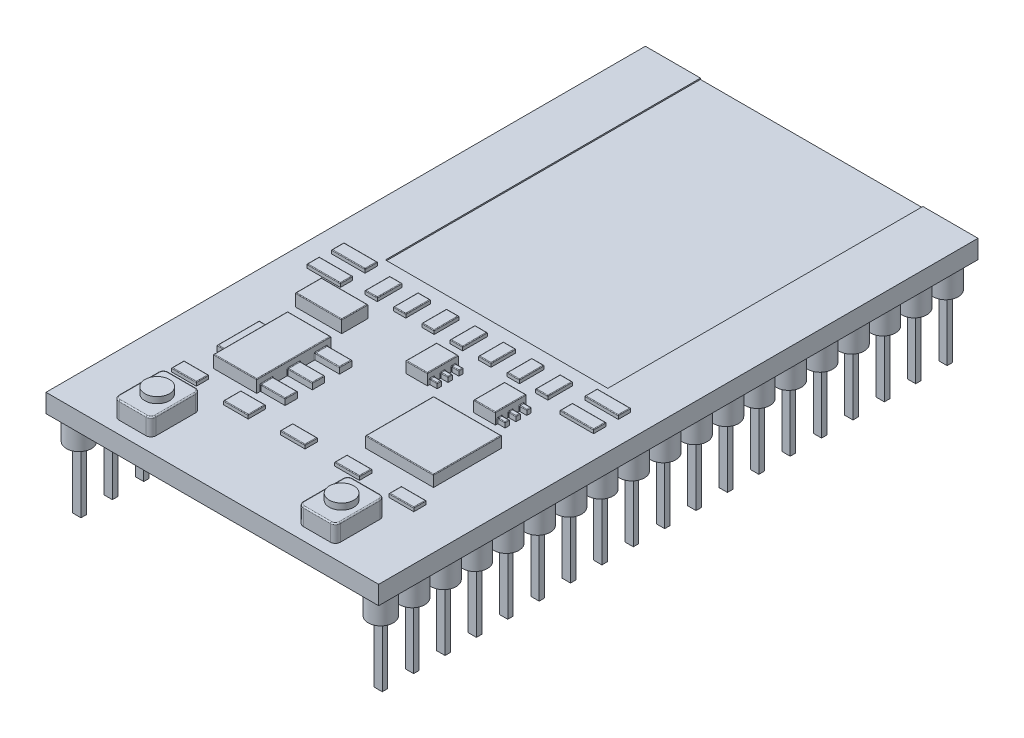
SolidWorks part; units mm, degrees
other "Markup1"
sketch "Sketch18" plane through (14.25, -8, 25.25) normal (0.0351, -0.9994, 0.0068) x (-0.8094, -0.0324, -0.5863)
sketch "Sketch19" plane through (14.25, -8, 25.25) normal (0.0351, -0.9994, 0.0068) x (-0.8094, -0.0324, -0.5863)
ref_plane "Alzado" through (0, 0, 0) normal (0, 0, 1) x (1, 0, 0)
ref_plane "Planta" through (0, 0, 0) normal (0, 1, 0) x (1, 0, 0)
ref_plane "Vista lateral" through (0, 0, 0) normal (1, 0, 0) x (0, 0, -1)
sketch "Sketch1" plane through (0, 0, 0) normal (0, 1, 0) x (1, 0, 0)
  line L0 (0, 0) -> (0, 24.257) construction
  line L1 (13.462, -24.257) -> (-13.462, -24.257)
  line L2 (13.462, -24.257) -> (13.462, 24.257)
  line L3 (13.462, 24.257) -> (-13.462, 24.257)
  line L4 (-13.462, -24.257) -> (-13.462, 24.257)
  line L5 (13.462, -24.257) -> (-13.462, 24.257) construction
  line L6 (13.462, 24.257) -> (-13.462, -24.257) construction
  line L7 (13.462, 0) -> (-13.462, 0) construction
  line L12 (11.462, 24.257) -> (11.462, 22.257) construction
  point P0 (0, 0)
  point P6 (13.462, 23.257)
  point P7 (12.462, 24.257)
  point P8 (17.05, 25.3)
  point P29 (11.462, 24.257)
  point P30 (-13.462, 24.257)
  point P31 (13.462, 24.257)
  point P32 (13.462, -24.257)
  point P33 (-13.462, -24.257)
  dimension "D1" = 48.514
  dimension "D2" = 26.924
  dimension "D3" = 1
  dimension "D4" = 1
  dimension "D6" = 2
  dimension "D7" = 2
extrude "Boss-Extrude1" add sketch "Sketch1" along normal blind 1.5 contours L1 L2 L3 L4 region at (0, 0, 0)
sketch "Sketch2" plane through (0, 0, 0) normal (0, -1, 0) x (1, 0, 0)
  line L0 (0, -24.257) -> (0, 24.257) construction
  line L1 (13.462, -24.257) -> (-13.462, -24.257) construction
  line L2 (13.462, 24.257) -> (-13.462, 24.257) construction
  line L3 (13.462, 0) -> (-13.462, 0) construction
  line L4 (13.462, 24.257) -> (13.462, -24.257) construction
  line L5 (-13.462, 24.257) -> (-13.462, -24.257) construction
  line L6 (-12.962, -23.0261) -> (-12.962, 24.257) construction
  line L7 (-12.962, -23.0261) -> (-12.962, -24.257) construction
  line L8 (-12.812, -19.067) -> (-12.712, -18.967)
  line L9 (-13.112, -18.567) -> (-12.812, -18.567)
  line L10 (-13.212, -18.667) -> (-13.212, -18.967)
  line L11 (-13.112, -19.067) -> (-12.812, -19.067)
  line L12 (-12.712, -18.667) -> (-12.712, -18.967)
  line L13 (-13.212, -18.567) -> (-12.712, -19.067) construction
  line L14 (-13.212, -19.067) -> (-12.712, -18.567) construction
  line L15 (-13.212, -18.967) -> (-13.112, -19.067)
  line L16 (-13.212, -18.667) -> (-13.112, -18.567)
  line L17 (-12.812, -18.567) -> (-12.712, -18.667)
  line L18 (-13.212, -16.427) -> (-13.112, -16.527)
  line L19 (-13.112, -16.527) -> (-12.812, -16.527)
  line L20 (-12.812, -16.527) -> (-12.712, -16.427)
  line L21 (-12.712, -16.127) -> (-12.712, -16.427)
  line L22 (-12.812, -16.027) -> (-12.712, -16.127)
  line L23 (-13.112, -16.027) -> (-12.812, -16.027)
  line L24 (-13.212, -16.127) -> (-13.112, -16.027)
  line L25 (-13.212, -16.127) -> (-13.212, -16.427)
  line L26 (-13.212, -13.887) -> (-13.112, -13.987)
  line L27 (-13.112, -13.987) -> (-12.812, -13.987)
  line L28 (-12.812, -13.987) -> (-12.712, -13.887)
  line L29 (-12.712, -13.587) -> (-12.712, -13.887)
  line L30 (-12.812, -13.487) -> (-12.712, -13.587)
  line L31 (-13.112, -13.487) -> (-12.812, -13.487)
  line L32 (-13.212, -13.587) -> (-13.112, -13.487)
  line L33 (-13.212, -13.587) -> (-13.212, -13.887)
  line L34 (-13.212, -11.347) -> (-13.112, -11.447)
  line L35 (-13.112, -11.447) -> (-12.812, -11.447)
  line L36 (-12.812, -11.447) -> (-12.712, -11.347)
  line L37 (-12.712, -11.047) -> (-12.712, -11.347)
  line L38 (-12.812, -10.947) -> (-12.712, -11.047)
  line L39 (-13.112, -10.947) -> (-12.812, -10.947)
  line L40 (-13.212, -11.047) -> (-13.112, -10.947)
  line L41 (-13.212, -11.047) -> (-13.212, -11.347)
  line L42 (-13.212, -8.807) -> (-13.112, -8.907)
  line L43 (-13.112, -8.907) -> (-12.812, -8.907)
  line L44 (-12.812, -8.907) -> (-12.712, -8.807)
  line L45 (-12.712, -8.507) -> (-12.712, -8.807)
  line L46 (-12.812, -8.407) -> (-12.712, -8.507)
  line L47 (-13.112, -8.407) -> (-12.812, -8.407)
  line L48 (-13.212, -8.507) -> (-13.112, -8.407)
  line L49 (-13.212, -8.507) -> (-13.212, -8.807)
  line L50 (-13.212, -6.267) -> (-13.112, -6.367)
  line L51 (-13.112, -6.367) -> (-12.812, -6.367)
  line L52 (-12.812, -6.367) -> (-12.712, -6.267)
  line L53 (-12.712, -5.967) -> (-12.712, -6.267)
  line L54 (-12.812, -5.867) -> (-12.712, -5.967)
  line L55 (-13.112, -5.867) -> (-12.812, -5.867)
  line L56 (-13.212, -5.967) -> (-13.112, -5.867)
  line L57 (-13.212, -5.967) -> (-13.212, -6.267)
  line L58 (-13.212, -3.727) -> (-13.112, -3.827)
  line L59 (-13.112, -3.827) -> (-12.812, -3.827)
  line L60 (-12.812, -3.827) -> (-12.712, -3.727)
  line L61 (-12.712, -3.427) -> (-12.712, -3.727)
  line L62 (-12.812, -3.327) -> (-12.712, -3.427)
  line L63 (-13.112, -3.327) -> (-12.812, -3.327)
  line L64 (-13.212, -3.427) -> (-13.112, -3.327)
  line L65 (-13.212, -3.427) -> (-13.212, -3.727)
  line L66 (-13.212, -1.187) -> (-13.112, -1.287)
  line L67 (-13.112, -1.287) -> (-12.812, -1.287)
  line L68 (-12.812, -1.287) -> (-12.712, -1.187)
  line L69 (-12.712, -0.887) -> (-12.712, -1.187)
  line L70 (-12.812, -0.787) -> (-12.712, -0.887)
  line L71 (-13.112, -0.787) -> (-12.812, -0.787)
  line L72 (-13.212, -0.887) -> (-13.112, -0.787)
  line L73 (-13.212, -0.887) -> (-13.212, -1.187)
  line L74 (-13.212, 1.353) -> (-13.112, 1.253)
  line L75 (-13.112, 1.253) -> (-12.812, 1.253)
  line L76 (-12.812, 1.253) -> (-12.712, 1.353)
  line L77 (-12.712, 1.653) -> (-12.712, 1.353)
  line L78 (-12.812, 1.753) -> (-12.712, 1.653)
  line L79 (-13.112, 1.753) -> (-12.812, 1.753)
  line L80 (-13.212, 1.653) -> (-13.112, 1.753)
  line L81 (-13.212, 1.653) -> (-13.212, 1.353)
  line L82 (-13.212, 3.893) -> (-13.112, 3.793)
  line L83 (-13.112, 3.793) -> (-12.812, 3.793)
  line L84 (-12.812, 3.793) -> (-12.712, 3.893)
  line L85 (-12.712, 4.193) -> (-12.712, 3.893)
  line L86 (-12.812, 4.293) -> (-12.712, 4.193)
  line L87 (-13.112, 4.293) -> (-12.812, 4.293)
  line L88 (-13.212, 4.193) -> (-13.112, 4.293)
  line L89 (-13.212, 4.193) -> (-13.212, 3.893)
  line L90 (-13.212, 6.433) -> (-13.112, 6.333)
  line L91 (-13.112, 6.333) -> (-12.812, 6.333)
  line L92 (-12.812, 6.333) -> (-12.712, 6.433)
  line L93 (-12.712, 6.733) -> (-12.712, 6.433)
  line L94 (-12.812, 6.833) -> (-12.712, 6.733)
  line L95 (-13.112, 6.833) -> (-12.812, 6.833)
  line L96 (-13.212, 6.733) -> (-13.112, 6.833)
  line L97 (-13.212, 6.733) -> (-13.212, 6.433)
  line L98 (-13.212, 8.973) -> (-13.112, 8.873)
  line L99 (-13.112, 8.873) -> (-12.812, 8.873)
  line L100 (-12.812, 8.873) -> (-12.712, 8.973)
  line L101 (-12.712, 9.273) -> (-12.712, 8.973)
  line L102 (-12.812, 9.373) -> (-12.712, 9.273)
  line L103 (-13.112, 9.373) -> (-12.812, 9.373)
  line L104 (-13.212, 9.273) -> (-13.112, 9.373)
  line L105 (-13.212, 9.273) -> (-13.212, 8.973)
  line L106 (-13.212, 11.513) -> (-13.112, 11.413)
  line L107 (-13.112, 11.413) -> (-12.812, 11.413)
  line L108 (-12.812, 11.413) -> (-12.712, 11.513)
  line L109 (-12.712, 11.813) -> (-12.712, 11.513)
  line L110 (-12.812, 11.913) -> (-12.712, 11.813)
  line L111 (-13.112, 11.913) -> (-12.812, 11.913)
  line L112 (-13.212, 11.813) -> (-13.112, 11.913)
  line L113 (-13.212, 11.813) -> (-13.212, 11.513)
  line L114 (-13.212, 14.053) -> (-13.112, 13.953)
  line L115 (-13.112, 13.953) -> (-12.812, 13.953)
  line L116 (-12.812, 13.953) -> (-12.712, 14.053)
  line L117 (-12.712, 14.353) -> (-12.712, 14.053)
  line L118 (-12.812, 14.453) -> (-12.712, 14.353)
  line L119 (-13.112, 14.453) -> (-12.812, 14.453)
  line L120 (-13.212, 14.353) -> (-13.112, 14.453)
  line L121 (-13.212, 14.353) -> (-13.212, 14.053)
  line L122 (-13.212, 16.593) -> (-13.112, 16.493)
  line L123 (-13.112, 16.493) -> (-12.812, 16.493)
  line L124 (-12.812, 16.493) -> (-12.712, 16.593)
  line L125 (-12.712, 16.893) -> (-12.712, 16.593)
  line L126 (-12.812, 16.993) -> (-12.712, 16.893)
  line L127 (-13.112, 16.993) -> (-12.812, 16.993)
  line L128 (-13.212, 16.893) -> (-13.112, 16.993)
  line L129 (-13.212, 16.893) -> (-13.212, 16.593)
  line L130 (12.812, 16.493) -> (12.712, 16.593)
  line L131 (12.712, 16.893) -> (12.712, 16.593)
  line L132 (12.812, 16.993) -> (12.712, 16.893)
  line L133 (13.112, 16.993) -> (12.812, 16.993)
  line L134 (13.212, 16.893) -> (13.112, 16.993)
  line L135 (13.212, 16.893) -> (13.212, 16.593)
  line L136 (13.212, 16.593) -> (13.112, 16.493)
  line L137 (13.112, 16.493) -> (12.812, 16.493)
  line L138 (13.212, 14.353) -> (13.212, 14.053)
  line L139 (13.212, 14.053) -> (13.112, 13.953)
  line L140 (13.112, 13.953) -> (12.812, 13.953)
  line L141 (12.812, 13.953) -> (12.712, 14.053)
  line L142 (12.712, 14.353) -> (12.712, 14.053)
  line L143 (12.812, 14.453) -> (12.712, 14.353)
  line L144 (13.112, 14.453) -> (12.812, 14.453)
  line L145 (13.212, 14.353) -> (13.112, 14.453)
  line L146 (13.212, 11.813) -> (13.212, 11.513)
  line L147 (13.212, 11.513) -> (13.112, 11.413)
  line L148 (13.112, 11.413) -> (12.812, 11.413)
  line L149 (12.812, 11.413) -> (12.712, 11.513)
  line L150 (12.712, 11.813) -> (12.712, 11.513)
  line L151 (12.812, 11.913) -> (12.712, 11.813)
  line L152 (13.112, 11.913) -> (12.812, 11.913)
  line L153 (13.212, 11.813) -> (13.112, 11.913)
  line L154 (13.212, 9.273) -> (13.212, 8.973)
  line L155 (13.212, 8.973) -> (13.112, 8.873)
  line L156 (13.112, 8.873) -> (12.812, 8.873)
  line L157 (12.812, 8.873) -> (12.712, 8.973)
  line L158 (12.712, 9.273) -> (12.712, 8.973)
  line L159 (12.812, 9.373) -> (12.712, 9.273)
  line L160 (13.112, 9.373) -> (12.812, 9.373)
  line L161 (13.212, 9.273) -> (13.112, 9.373)
  line L162 (13.212, 6.733) -> (13.212, 6.433)
  line L163 (13.212, 6.433) -> (13.112, 6.333)
  line L164 (13.112, 6.333) -> (12.812, 6.333)
  line L165 (12.812, 6.333) -> (12.712, 6.433)
  line L166 (12.712, 6.733) -> (12.712, 6.433)
  line L167 (12.812, 6.833) -> (12.712, 6.733)
  line L168 (13.112, 6.833) -> (12.812, 6.833)
  line L169 (13.212, 6.733) -> (13.112, 6.833)
  line L170 (13.212, 4.193) -> (13.212, 3.893)
  line L171 (13.212, 3.893) -> (13.112, 3.793)
  line L172 (13.112, 3.793) -> (12.812, 3.793)
  line L173 (12.812, 3.793) -> (12.712, 3.893)
  line L174 (12.712, 4.193) -> (12.712, 3.893)
  line L175 (12.812, 4.293) -> (12.712, 4.193)
  line L176 (13.112, 4.293) -> (12.812, 4.293)
  line L177 (13.212, 4.193) -> (13.112, 4.293)
  line L178 (13.212, 1.653) -> (13.212, 1.353)
  line L179 (13.212, 1.353) -> (13.112, 1.253)
  line L180 (13.112, 1.253) -> (12.812, 1.253)
  line L181 (12.812, 1.253) -> (12.712, 1.353)
  line L182 (12.712, 1.653) -> (12.712, 1.353)
  line L183 (12.812, 1.753) -> (12.712, 1.653)
  line L184 (13.112, 1.753) -> (12.812, 1.753)
  line L185 (13.212, 1.653) -> (13.112, 1.753)
  line L186 (13.212, -0.887) -> (13.212, -1.187)
  line L187 (13.212, -1.187) -> (13.112, -1.287)
  line L188 (13.112, -1.287) -> (12.812, -1.287)
  line L189 (12.812, -1.287) -> (12.712, -1.187)
  line L190 (12.712, -0.887) -> (12.712, -1.187)
  line L191 (12.812, -0.787) -> (12.712, -0.887)
  line L192 (13.112, -0.787) -> (12.812, -0.787)
  line L193 (13.212, -0.887) -> (13.112, -0.787)
  line L194 (13.212, -3.427) -> (13.212, -3.727)
  line L195 (13.212, -3.727) -> (13.112, -3.827)
  line L196 (13.112, -3.827) -> (12.812, -3.827)
  line L197 (12.812, -3.827) -> (12.712, -3.727)
  line L198 (12.712, -3.427) -> (12.712, -3.727)
  line L199 (12.812, -3.327) -> (12.712, -3.427)
  line L200 (13.112, -3.327) -> (12.812, -3.327)
  line L201 (13.212, -3.427) -> (13.112, -3.327)
  line L202 (13.212, -5.967) -> (13.212, -6.267)
  line L203 (13.212, -6.267) -> (13.112, -6.367)
  line L204 (13.112, -6.367) -> (12.812, -6.367)
  line L205 (12.812, -6.367) -> (12.712, -6.267)
  line L206 (12.712, -5.967) -> (12.712, -6.267)
  line L207 (12.812, -5.867) -> (12.712, -5.967)
  line L208 (13.112, -5.867) -> (12.812, -5.867)
  line L209 (13.212, -5.967) -> (13.112, -5.867)
  line L210 (13.212, -8.507) -> (13.212, -8.807)
  line L211 (13.212, -8.807) -> (13.112, -8.907)
  line L212 (13.112, -8.907) -> (12.812, -8.907)
  line L213 (12.812, -8.907) -> (12.712, -8.807)
  line L214 (12.712, -8.507) -> (12.712, -8.807)
  line L215 (12.812, -8.407) -> (12.712, -8.507)
  line L216 (13.112, -8.407) -> (12.812, -8.407)
  line L217 (13.212, -8.507) -> (13.112, -8.407)
  line L218 (13.212, -11.047) -> (13.212, -11.347)
  line L219 (13.212, -11.347) -> (13.112, -11.447)
  line L220 (13.112, -11.447) -> (12.812, -11.447)
  line L221 (12.812, -11.447) -> (12.712, -11.347)
  line L222 (12.712, -11.047) -> (12.712, -11.347)
  line L223 (12.812, -10.947) -> (12.712, -11.047)
  line L224 (13.112, -10.947) -> (12.812, -10.947)
  line L225 (13.212, -11.047) -> (13.112, -10.947)
  line L226 (13.212, -13.587) -> (13.212, -13.887)
  line L227 (13.212, -13.887) -> (13.112, -13.987)
  line L228 (13.112, -13.987) -> (12.812, -13.987)
  line L229 (12.812, -13.987) -> (12.712, -13.887)
  line L230 (12.712, -13.587) -> (12.712, -13.887)
  line L231 (12.812, -13.487) -> (12.712, -13.587)
  line L232 (13.112, -13.487) -> (12.812, -13.487)
  line L233 (13.212, -13.587) -> (13.112, -13.487)
  line L234 (13.212, -16.127) -> (13.212, -16.427)
  line L235 (13.212, -16.427) -> (13.112, -16.527)
  line L236 (13.112, -16.527) -> (12.812, -16.527)
  line L237 (12.812, -16.527) -> (12.712, -16.427)
  line L238 (12.712, -16.127) -> (12.712, -16.427)
  line L239 (12.812, -16.027) -> (12.712, -16.127)
  line L240 (13.112, -16.027) -> (12.812, -16.027)
  line L241 (13.212, -16.127) -> (13.112, -16.027)
  line L242 (13.212, -18.667) -> (13.212, -18.967)
  line L243 (13.212, -18.967) -> (13.112, -19.067)
  line L244 (13.112, -19.067) -> (12.812, -19.067)
  line L245 (12.812, -19.067) -> (12.712, -18.967)
  line L246 (12.712, -18.667) -> (12.712, -18.967)
  line L247 (12.812, -18.567) -> (12.712, -18.667)
  line L248 (13.112, -18.567) -> (12.812, -18.567)
  line L249 (13.212, -18.667) -> (13.112, -18.567)
  point P12 (-14.25, -25.25)
  point P13 (-13.462, -21.6118)
  point P14 (-12.962, -23.0261)
  point P18 (-12.962, -18.817)
  point P19 (-12.962, -18.817)
  dimension "D1" = 1.5
  dimension "D2" = 5.44
  dimension "D3" = 0.5
  dimension "D4" = 0.5
  dimension "D5" = 15
  dimension "D6" = 15
sketch "Sketch5" plane through (0, 1.5, 0) normal (0, 1, 0) x (1, 0, 0)
  line L0 (-13.462, -23.257) -> (-8.962, -23.257) construction
  line L1 (0, -24.257) -> (0, 24.257) construction
  line L2 (-8.562, -23.257) -> (-6.362, -23.257)
  line L3 (-8.962, -22.857) -> (-8.962, -19.657)
  line L4 (-8.562, -19.257) -> (-6.362, -19.257)
  line L5 (-5.962, -22.857) -> (-5.962, -19.657)
  line L6 (13.462, -24.257) -> (-13.462, -24.257) construction
  line L7 (13.462, 24.257) -> (-13.462, 24.257) construction
  line L8 (5.962, -22.857) -> (5.962, -19.657)
  line L9 (8.562, -23.257) -> (6.362, -23.257)
  line L10 (8.962, -22.857) -> (8.962, -19.657)
  line L11 (8.562, -19.257) -> (6.362, -19.257)
  arc A0 (-8.962, -22.857) -> (-8.562, -23.257) centre (-8.562, -22.857) ccw
  arc A1 (-6.362, -23.257) -> (-5.962, -22.857) centre (-6.362, -22.857) ccw
  arc A2 (-6.362, -19.257) -> (-5.962, -19.657) centre (-6.362, -19.657) cw
  arc A3 (-8.962, -19.657) -> (-8.562, -19.257) centre (-8.562, -19.657) cw
  arc A4 (6.362, -23.257) -> (5.962, -22.857) centre (6.362, -22.857) cw
  arc A5 (8.962, -22.857) -> (8.562, -23.257) centre (8.562, -22.857) cw
  arc A6 (8.962, -19.657) -> (8.562, -19.257) centre (8.562, -19.657) ccw
  arc A7 (6.362, -19.257) -> (5.962, -19.657) centre (6.362, -19.657) ccw
  point P11 (-5.962, -23.257)
  point P14 (-5.962, -19.257)
  point P17 (-8.962, -19.257)
  dimension "D4" = 0.4
  dimension "D1" = 4.5
  dimension "D2" = 4
  dimension "D3" = 3
extrude "Boss-Extrude5" add sketch "Sketch5" along normal blind 1.4
sketch "Sketch6" plane through (0, 2.9, 0) normal (0, 1, 0) x (1, 0, 0)
  line L0 (-8.962, -21.257) -> (-5.962, -21.257) construction
  line L1 (-8.962, -19.657) -> (-8.962, -22.857) construction
  line L2 (-5.962, -22.857) -> (-5.962, -19.657) construction
  line L3 (0, -24.257) -> (0, 24.257) construction
  line L4 (13.462, -24.257) -> (-13.462, -24.257) construction
  line L5 (13.462, 24.257) -> (-13.462, 24.257) construction
  circle A0 centre (-7.462, -21.257) radius 0.9958
  circle A1 centre (7.462, -21.257) radius 0.9958
extrude "Boss-Extrude6" add sketch "Sketch6" along normal blind 0.5
sketch "Sketch7" plane through (0, 1.5, 0) normal (0, 1, 0) x (1, 0, 0)
  line L0 (13.462, 24.257) -> (-13.462, 24.257) construction
  line L1 (0, 24.257) -> (0, 0) construction
  line L3 (-9, 24.257) -> (9, 24.257)
  line L4 (-9, 24.257) -> (-9, -1.243)
  line L5 (-9, -1.243) -> (9, -1.243)
  line L6 (9, 24.257) -> (9, -1.243)
  point P0 (0, 24.257)
  point P5 (-9, 24.257)
  dimension "D1" = 9
  dimension "D2" = 18
  dimension "D3" = 25.5
extrude "Cut-Extrude1" cut sketch "Sketch7" against normal blind 0.1
sketch "Sketch8" plane through (0, 1.5, 0) normal (0, 1, 0) x (1, 0, 0)
  line L0 (13.462, -24.257) -> (-13.462, -24.257) construction
  line L1 (0, -24.257) -> (0, 0) construction
  line L2 (2.8, -4.5) -> (2.8, -2.5)
  line L3 (0.5, -4.5) -> (-0.5, -4.5)
  line L4 (1, -17.75) -> (-1, -17.75)
  line L5 (1, -17.75) -> (1, -16.75)
  line L6 (1, -16.75) -> (-1, -16.75)
  line L7 (-1, -17.75) -> (-1, -16.75)
  line L8 (1, -17.75) -> (-1, -16.75) construction
  line L9 (1, -16.75) -> (-1, -17.75) construction
  line L10 (-3.4, -17.95) -> (-5.4, -17.95)
  line L11 (-3.4, -17.95) -> (-3.4, -16.55)
  line L12 (-3.4, -16.55) -> (-5.4, -16.55)
  line L13 (-5.4, -17.95) -> (-5.4, -16.55)
  line L14 (-3.4, -17.95) -> (-5.4, -16.55) construction
  line L15 (-3.4, -16.55) -> (-5.4, -17.95) construction
  line L16 (-9.8, -17.75) -> (-7.8, -17.75)
  line L17 (-9.8, -17.75) -> (-9.8, -16.75)
  line L18 (-9.8, -16.75) -> (-7.8, -16.75)
  line L19 (-7.8, -17.75) -> (-7.8, -16.75)
  line L20 (-9.8, -17.75) -> (-7.8, -16.75) construction
  line L21 (-9.8, -16.75) -> (-7.8, -17.75) construction
  line L22 (5.4, -17.75) -> (3.4, -17.75)
  line L23 (5.4, -17.75) -> (5.4, -16.75)
  line L24 (5.4, -16.75) -> (3.4, -16.75)
  line L25 (3.4, -17.75) -> (3.4, -16.75)
  line L26 (5.4, -17.75) -> (3.4, -16.75) construction
  line L27 (5.4, -16.75) -> (3.4, -17.75) construction
  line L28 (9.8, -17.75) -> (7.8, -17.75)
  line L29 (9.8, -17.75) -> (9.8, -16.75)
  line L30 (9.8, -16.75) -> (7.8, -16.75)
  line L31 (7.8, -17.75) -> (7.8, -16.75)
  line L32 (9.8, -17.75) -> (7.8, -16.75) construction
  line L33 (9.8, -16.75) -> (7.8, -17.75) construction
  line L34 (0.5, -4.5) -> (0.5, -2.5)
  line L35 (0.5, -2.5) -> (-0.5, -2.5)
  line L36 (-0.5, -4.5) -> (-0.5, -2.5)
  line L37 (0.5, -4.5) -> (-0.5, -2.5) construction
  line L38 (0.5, -2.5) -> (-0.5, -4.5) construction
  line L39 (2.8, -2.5) -> (1.8, -2.5)
  line L40 (1.8, -4.5) -> (1.8, -2.5)
  line L41 (2.8, -4.5) -> (1.8, -4.5)
  line L42 (5.1, -4.5) -> (5.1, -2.5)
  line L43 (5.1, -2.5) -> (4.1, -2.5)
  line L44 (4.1, -4.5) -> (4.1, -2.5)
  line L45 (5.1, -4.5) -> (4.1, -4.5)
  line L46 (7.4, -4.5) -> (7.4, -2.5)
  line L47 (7.4, -2.5) -> (6.4, -2.5)
  line L48 (6.4, -4.5) -> (6.4, -2.5)
  line L49 (7.4, -4.5) -> (6.4, -4.5)
  line L50 (-7.4, -4.5) -> (-6.4, -4.5)
  line L51 (-6.4, -4.5) -> (-6.4, -2.5)
  line L52 (-7.4, -2.5) -> (-6.4, -2.5)
  line L53 (-7.4, -4.5) -> (-7.4, -2.5)
  line L54 (-5.1, -4.5) -> (-4.1, -4.5)
  line L55 (-4.1, -4.5) -> (-4.1, -2.5)
  line L56 (-5.1, -2.5) -> (-4.1, -2.5)
  line L57 (-5.1, -4.5) -> (-5.1, -2.5)
  line L58 (-2.8, -4.5) -> (-1.8, -4.5)
  line L59 (-1.8, -4.5) -> (-1.8, -2.5)
  line L60 (-2.8, -2.5) -> (-1.8, -2.5)
  line L61 (-2.8, -4.5) -> (-2.8, -2.5)
  line L62 (7.4, -3.5) -> (13.462, -3.5) construction
  line L63 (13.462, -24.257) -> (13.462, 24.257) construction
  line L64 (11.6049, -3) -> (11.6049, -2)
  line L65 (11.6049, -5) -> (8.8951, -5)
  line L66 (11.6049, -5) -> (11.6049, -4)
  line L67 (11.6049, -2) -> (8.8951, -2)
  line L68 (8.8951, -5) -> (8.8951, -4)
  line L69 (11.6049, -5) -> (8.8951, -2) construction
  line L70 (11.6049, -2) -> (8.8951, -5) construction
  line L71 (11.6049, -4) -> (8.8951, -4)
  line L72 (8.8951, -3) -> (8.8951, -2)
  line L73 (11.6049, -3) -> (8.8951, -3)
  line L74 (-11.6049, -5) -> (-8.8951, -5)
  line L75 (11.6049, -4) -> (8.8951, -3) construction
  line L76 (11.6049, -3) -> (8.8951, -4) construction
  line L77 (-8.8951, -5) -> (-8.8951, -4)
  line L78 (-11.6049, -4) -> (-8.8951, -4)
  line L79 (-11.6049, -5) -> (-11.6049, -4)
  line L80 (-11.6049, -3) -> (-11.6049, -2)
  line L81 (-11.6049, -3) -> (-8.8951, -3)
  line L82 (-8.8951, -3) -> (-8.8951, -2)
  line L83 (-11.6049, -2) -> (-8.8951, -2)
  point P0 (0, -24.257)
  point P6 (0, -17.25)
  point P7 (-4.4, -17.25)
  point P8 (-8.8, -17.25)
  point P9 (-4.4, -17.25)
  point P10 (0, -17.25)
  point P17 (4.4, -17.25)
  point P18 (8.8, -17.25)
  point P21 (-8.8, -17.25)
  point P26 (4.4, -17.25)
  point P31 (8.8, -17.25)
  point P36 (0, -3.5)
  point P37 (0, -3.5)
  point P70 (10.25, -3.5)
  point P71 (10.25, -3.5)
  point P76 (10.25, -3.5)
  dimension "D1" = 3
  dimension "D2" = 2
  dimension "D3" = 1
  dimension "D4" = 2
  dimension "D5" = 1.4
  dimension "D6" = 2
  dimension "D7" = 1
  dimension "D8" = 2
  dimension "D9" = 2
  dimension "D11" = 1
extrude "Boss-Extrude7" add sketch "Sketch8" along normal blind 0.3
sketch "Sketch9" plane through (0, 1.5, 0) normal (0, 1, 0) x (1, 0, 0)
  line L0 (3.4, -16.75) -> (3.4, -1.243) construction
  line L1 (-9, -1.243) -> (9, -1.243) construction
  line L2 (5.1, -4.5) -> (6.4, -4.5) construction
  line L3 (3.4, -15.25) -> (8.9, -15.25)
  line L4 (3.4, -15.25) -> (3.4, -9.75)
  line L5 (3.4, -9.75) -> (8.9, -9.75)
  line L6 (8.9, -15.25) -> (8.9, -9.75)
  line L7 (6.15, -9.75) -> (6.15, -4.5) construction
  line L8 (-0.225, -8.375) -> (-0.225, -5.875)
  line L9 (7.025, -8.375) -> (5.275, -8.375)
  line L10 (7.025, -8.375) -> (7.025, -5.875)
  line L11 (7.025, -5.875) -> (5.275, -5.875)
  line L12 (5.275, -8.375) -> (5.275, -5.875)
  line L13 (7.025, -8.375) -> (5.275, -5.875) construction
  line L14 (7.025, -5.875) -> (5.275, -8.375) construction
  line L15 (-0.225, -8.375) -> (1.525, -8.375)
  line L16 (1.525, -8.375) -> (1.525, -5.875)
  line L17 (-0.225, -5.875) -> (1.525, -5.875)
  point P5 (3.4, -15.25)
  point P16 (6.15, -7.125)
  point P17 (6.15, -7.125)
  dimension "D1" = 1.75
  dimension "D2" = 1.5
  dimension "D3" = 5.5
  dimension "D4" = 2.5
  dimension "D5" = 5.5
extrude "Boss-Extrude8" add sketch "Sketch9" along normal blind 0.9
sketch "Sketch10" plane through (0, 1.5, 0) normal (0, 1, 0) x (1, 0, 0)
  line L0 (-9.8, -17.25) -> (-3.4, -17.25) construction
  line L1 (-9.8, -16.75) -> (-9.8, -17.75) construction
  line L2 (-3.4, -17.95) -> (-3.4, -16.55) construction
  line L3 (-0.225, -8.375) -> (-13.462, -8.375) construction
  line L4 (-13.462, -24.257) -> (-13.462, 24.257) construction
  line L5 (-6.6, -17.25) -> (-6.6, -8.375) construction
  line L7 (-4.85, -15.8125) -> (-8.35, -15.8125)
  line L8 (-4.85, -15.8125) -> (-4.85, -9.8125)
  line L9 (-4.85, -9.8125) -> (-8.35, -9.8125)
  line L10 (-8.35, -15.8125) -> (-8.35, -9.8125)
  line L11 (-4.85, -15.8125) -> (-8.35, -9.8125) construction
  line L12 (-4.85, -9.8125) -> (-8.35, -15.8125) construction
  point P13 (-6.6, -12.8125)
  dimension "D1" = 6
  dimension "D2" = 3.5
extrude "Boss-Extrude9" add sketch "Sketch10" along normal blind 1
sketch "Sketch11" plane through (0, 1.5, 0) normal (0, 1, 0) x (1, 0, 0)
  line L0 (-4.85, -12.8125) -> (-8.35, -12.8125) construction
  line L1 (-4.85, -15.8125) -> (-4.85, -9.8125) construction
  line L2 (-8.35, -9.8125) -> (-8.35, -15.8125) construction
  line L3 (-4.85, -12.8125) -> (-4.85, -11.1125) construction
  line L4 (-4.85, -15.8125) -> (-4.85, -9.8125) construction
  line L5 (-4.85, -12.3125) -> (-2.85, -12.3125)
  line L6 (-4.85, -11.1125) -> (-2.85, -11.1125)
  line L7 (-4.85, -11.1125) -> (-4.85, -10.1125)
  line L8 (-4.85, -10.1125) -> (-2.85, -10.1125)
  line L9 (-2.85, -11.1125) -> (-2.85, -10.1125)
  line L10 (-2.85, -13.3125) -> (-2.85, -12.3125)
  line L11 (-4.85, -13.3125) -> (-4.85, -12.3125)
  line L12 (-4.85, -13.3125) -> (-2.85, -13.3125)
  line L13 (-4.85, -14.5125) -> (-2.85, -14.5125)
  line L14 (-2.85, -15.5125) -> (-2.85, -14.5125)
  line L15 (-4.85, -15.5125) -> (-4.85, -14.5125)
  line L16 (-4.85, -15.5125) -> (-2.85, -15.5125)
  line L17 (-4.85, -14.5125) -> (-8.35, -14.5125) construction
  line L18 (-8.35, -9.8125) -> (-8.35, -15.8125) construction
  line L20 (-8.35, -14.5125) -> (-9.35, -14.5125)
  line L21 (-8.35, -14.5125) -> (-8.35, -11.1125)
  line L22 (-8.35, -11.1125) -> (-9.35, -11.1125)
  line L23 (-9.35, -14.5125) -> (-9.35, -11.1125)
  dimension "D1" = 1
  dimension "D2" = 2
  dimension "D3" = 1
  dimension "D4" = 3
extrude "Boss-Extrude10" add sketch "Sketch11" along normal blind 0.5
sketch "Sketch12" plane through (0, 1.5, 0) normal (0, 1, 0) x (1, 0, 0)
  line L0 (7.025, -7.125) -> (5.275, -7.125) construction
  line L1 (7.025, -8.375) -> (7.025, -5.875) construction
  line L2 (5.275, -5.875) -> (5.275, -8.375) construction
  line L3 (7.025, -7.125) -> (7.025, -6.425) construction
  line L4 (7.025, -7.305) -> (7.625, -7.305)
  line L5 (7.025, -6.425) -> (7.625, -6.425)
  line L6 (7.025, -6.425) -> (7.025, -6.075)
  line L7 (7.025, -6.075) -> (7.625, -6.075)
  line L8 (7.625, -6.425) -> (7.625, -6.075)
  line L9 (7.025, -7.305) -> (7.025, -6.955)
  line L10 (7.025, -6.955) -> (7.625, -6.955)
  line L11 (7.625, -7.305) -> (7.625, -6.955)
  line L12 (7.025, -8.185) -> (7.625, -8.185)
  line L13 (7.025, -8.185) -> (7.025, -7.835)
  line L14 (7.025, -7.835) -> (7.625, -7.835)
  line L15 (7.625, -8.185) -> (7.625, -7.835)
  line L16 (1.525, -7.125) -> (-0.225, -7.125) construction
  line L17 (1.525, -8.375) -> (1.525, -5.875) construction
  line L18 (-0.225, -5.875) -> (-0.225, -8.375) construction
  line L19 (1.525, -7.125) -> (1.525, -6.425) construction
  line L20 (1.525, -6.955) -> (2.125, -6.955)
  line L21 (1.525, -6.425) -> (2.125, -6.425)
  line L22 (1.525, -6.425) -> (1.525, -6.075)
  line L23 (1.525, -6.075) -> (2.125, -6.075)
  line L24 (2.125, -6.425) -> (2.125, -6.075)
  line L25 (1.525, -7.305) -> (1.525, -6.955)
  line L26 (2.125, -7.305) -> (2.125, -6.955)
  line L27 (1.525, -7.305) -> (2.125, -7.305)
  line L28 (1.525, -7.835) -> (2.125, -7.835)
  line L29 (1.525, -8.185) -> (1.525, -7.835)
  line L30 (2.125, -8.185) -> (2.125, -7.835)
  line L31 (1.525, -8.185) -> (2.125, -8.185)
  line L32 (-0.225, -5.875) -> (-0.225, -8.375) construction
  line L33 (-0.225, -7.835) -> (-0.725, -7.835)
  line L34 (-0.225, -7.835) -> (-0.225, -6.425)
  line L35 (-0.225, -6.425) -> (-0.725, -6.425)
  line L36 (-0.725, -7.835) -> (-0.725, -6.425)
  line L37 (5.275, -5.875) -> (5.275, -8.375) construction
  line L38 (5.275, -7.835) -> (4.775, -7.835)
  line L39 (5.275, -7.835) -> (5.275, -6.425)
  line L40 (5.275, -6.425) -> (4.775, -6.425)
  line L41 (4.775, -7.835) -> (4.775, -6.425)
  dimension "D1" = 0.7
  dimension "D2" = 0.6
  dimension "D3" = 0.35
  dimension "D5" = 0.7
  dimension "D6" = 0.6
  dimension "D8" = 0.5
  dimension "D9" = 0.5
  dimension "D4" = 3
  dimension "D7" = 3
extrude "Boss-Extrude11" add sketch "Sketch12" along normal blind 0.4
sketch "Sketch13" plane through (0, 1.5, 0) normal (0, 1, 0) x (1, 0, 0)
  line L0 (1.525, -6.075) -> (-13.462, -6.075) construction
  line L1 (-13.462, -24.257) -> (-13.462, 24.257) construction
  line L2 (1.525, -8.185) -> (-13.462, -8.185) construction
  line L3 (-9.35, -11.1125) -> (-9.35, -8.185) construction
  line L4 (-8.35, -11.1125) -> (-9.35, -11.1125) construction
  line L6 (-9.35, -8.185) -> (-5.6, -8.185)
  line L7 (-9.35, -8.185) -> (-9.35, -6.075)
  line L8 (-9.35, -6.075) -> (-5.6, -6.075)
  line L9 (-5.6, -8.185) -> (-5.6, -6.075)
  dimension "D1" = 3.75
extrude "Boss-Extrude12" add sketch "Sketch13" along normal blind 1
fillet "Fillet8" radius 0.05 84 edges at (10.25, 1.8, 5) (8.8951, 1.8, 4.5) (10.25, 1.8, 4) (11.6049, 1.8, 4.5) (10.25, 1.8, 2) (11.6049, 1.8, 2.5) (10.25, 1.8, 3) (8.8951, 1.8, 2.5) (6.9, 1.8, 2.5) (7.4, 1.8, 3.5) (6.9, 1.8, 4.5) (6.4, 1.8, 3.5) (4.6, 1.8, 2.5) (5.1, 1.8, 3.5) (4.6, 1.8, 4.5) (4.1, 1.8, 3.5) (2.3, 1.8, 2.5) (2.8, 1.8, 3.5) (2.3, 1.8, 4.5) (1.8, 1.8, 3.5) (0, 1.8, 2.5) (0.5, 1.8, 3.5) (0, 1.8, 4.5) (-0.5, 1.8, 3.5) (-2.3, 1.8, 2.5) (-1.8, 1.8, 3.5) (-2.3, 1.8, 4.5) (-2.8, 1.8, 3.5) (-4.6, 1.8, 2.5) (-4.1, 1.8, 3.5) (-4.6, 1.8, 4.5) (-5.1, 1.8, 3.5) (-10.25, 1.8, 4) (-8.8951, 1.8, 4.5) (-10.25, 1.8, 5) (-11.6049, 1.8, 4.5) (-11.6049, 1.8, 2.5) (-10.25, 1.8, 2) (-8.8951, 1.8, 2.5) (-10.25, 1.8, 3) (-6.9, 1.8, 2.5) (-6.4, 1.8, 3.5) (-6.9, 1.8, 4.5) (-7.4, 1.8, 3.5) (-7.475, 2.5, 6.075) (-5.6, 2.5, 7.13) (-7.475, 2.5, 8.185) (-9.35, 2.5, 7.13) (-0.225, 2.4, 7.125) (0.65, 2.4, 5.875) (1.525, 2.4, 7.125) (0.65, 2.4, 8.375) (6.15, 2.4, 5.875) (7.025, 2.4, 7.125) (6.15, 2.4, 8.375) (5.275, 2.4, 7.125) (-6.6, 2.5, 9.8125) (-4.85, 2.5, 12.8125) (-6.6, 2.5, 15.8125) (-8.35, 2.5, 12.8125) (6.15, 2.4, 9.75) (8.9, 2.4, 12.5) (6.15, 2.4, 15.25) (3.4, 2.4, 12.5) (-8.8, 1.8, 17.75) (-9.8, 1.8, 17.25) (-8.8, 1.8, 16.75) (-7.8, 1.8, 17.25) (-4.4, 1.8, 16.55) (-3.4, 1.8, 17.25) (-4.4, 1.8, 17.95) (-5.4, 1.8, 17.25) (0, 1.8, 16.75) (1, 1.8, 17.25) (0, 1.8, 17.75) (-1, 1.8, 17.25) (4.4, 1.8, 16.75) (5.4, 1.8, 17.25) (4.4, 1.8, 17.75) (3.4, 1.8, 17.25) (8.8, 1.8, 16.75) (9.8, 1.8, 17.25) (8.8, 1.8, 17.75) (7.8, 1.8, 17.25)
fillet "Fillet9" radius 0.05 72 edges at (-0.225, 1.7, 7.835) (-0.225, 1.7, 6.425) (1.525, 1.7, 6.075) (1.525, 1.7, 6.425) (1.525, 1.7, 6.955) (1.525, 1.7, 7.305) (1.525, 1.7, 7.835) (1.525, 1.7, 8.185) (5.275, 1.7, 7.835) (5.275, 1.7, 6.425) (7.025, 1.7, 6.075) (7.025, 1.7, 6.425) (7.025, 1.7, 6.955) (7.025, 1.7, 7.305) (7.025, 1.7, 7.835) (7.025, 1.7, 8.185) (-4.85, 1.75, 15.5125) (-4.85, 1.75, 14.5125) (-4.85, 1.75, 11.1125) (-4.85, 1.75, 10.1125) (-4.85, 1.75, 13.3125) (-4.85, 1.75, 12.3125) (-8.35, 1.75, 14.5125) (-8.35, 1.75, 11.1125) (-0.475, 1.9, 7.835) (-0.725, 1.9, 7.13) (-0.475, 1.9, 6.425) (-0.225, 1.9, 7.13) (1.825, 1.9, 6.075) (2.125, 1.9, 6.25) (1.825, 1.9, 6.425) (1.525, 1.9, 6.25) (1.525, 1.9, 7.13) (1.825, 1.9, 6.955) (2.125, 1.9, 7.13) (1.825, 1.9, 7.305) (1.525, 1.9, 8.01) (1.825, 1.9, 7.835) (2.125, 1.9, 8.01) (1.825, 1.9, 8.185) (5.025, 1.9, 7.835) (4.775, 1.9, 7.13) (5.025, 1.9, 6.425) (5.275, 1.9, 7.13) (7.325, 1.9, 6.075) (7.625, 1.9, 6.25) (7.325, 1.9, 6.425) (7.025, 1.9, 6.25) (7.325, 1.9, 6.955) (7.625, 1.9, 7.13) (7.325, 1.9, 7.305) (7.025, 1.9, 7.13) (7.325, 1.9, 7.835) (7.625, 1.9, 8.01) (7.325, 1.9, 8.185) (7.025, 1.9, 8.01) (-3.85, 2, 15.5125) (-4.85, 2, 15.0125) (-3.85, 2, 14.5125) (-2.85, 2, 15.0125) (-3.85, 2, 11.1125) (-4.85, 2, 10.6125) (-3.85, 2, 10.1125) (-2.85, 2, 10.6125) (-3.85, 2, 13.3125) (-4.85, 2, 12.8125) (-3.85, 2, 12.3125) (-2.85, 2, 12.8125) (-8.85, 2, 14.5125) (-9.35, 2, 12.8125) (-8.85, 2, 11.1125) (-8.35, 2, 12.8125)
fillet "Fillet10" radius 0.1 16 edges at (-6.0792, 2.9, 19.3742) (-5.962, 2.9, 21.257) (-6.0792, 2.9, 23.1398) (-7.462, 2.9, 23.257) (-8.8448, 2.9, 23.1398) (-8.962, 2.9, 21.257) (-8.8448, 2.9, 19.3742) (8.8448, 2.9, 19.3742) (8.962, 2.9, 21.257) (8.8448, 2.9, 23.1398) (7.462, 2.9, 23.257) (6.0792, 2.9, 23.1398) (5.962, 2.9, 21.257) (6.0792, 2.9, 19.3742) (-7.462, 2.9, 19.257) (7.462, 2.9, 19.257)
sketch "Sketch14" plane through (0, 0, 0) normal (0, -1, 0) x (1, 0, 0)
  text T0 "A.Patiño" font "Century Gothic" height in points 8
sketch "Sketch15" plane through (0, 1.5, 0) normal (0, 1, 0) x (1, 0, 0)
  line L0 (13.462, -24.257) -> (-13.462, -24.257) construction
  line L1 (0, 0) -> (0, -24.257) construction
  line L2 (2.595, -24.257) -> (-2.595, -24.257)
  line L3 (2.595, -24.257) -> (2.595, -23.907) construction
  line L5 (2.595, -23.907) -> (0.735, -23.907)
  line L6 (2.595, -23.907) -> (2.595, -23.457)
  line L7 (2.595, -23.457) -> (0.735, -23.457)
  line L8 (0.735, -23.907) -> (0.735, -23.457)
  point P0 (0, -24.257)
  point P9 (0, -24.257)
  dimension "D1" = 5.19
  dimension "D2" = 0.35
  dimension "D3" = 0.45
  dimension "D4" = 1.86
sketch "Sketch23" plane through (0, 0, 0) normal (0, -1, 0) x (-1, 0, 0)
  line L0 (0, 24.257) -> (0, -24.257) construction
  line L1 (-13.462, 24.257) -> (13.462, 24.257) construction
  line L2 (11.912, -20.5993) -> (11.912, -19.9897)
  line L3 (12.5216, -23.1393) -> (11.912, -23.1393)
  line L4 (12.5216, -23.1393) -> (12.5216, -22.5297)
  line L5 (12.5216, -22.5297) -> (11.912, -22.5297)
  line L6 (11.912, -23.1393) -> (11.912, -22.5297)
  line L7 (12.5216, -23.1393) -> (11.912, -22.5297) construction
  line L8 (12.5216, -22.5297) -> (11.912, -23.1393) construction
  line L9 (12.5216, -20.5993) -> (11.912, -20.5993)
  line L10 (12.5216, -20.5993) -> (12.5216, -19.9897)
  line L11 (12.5216, -19.9897) -> (11.912, -19.9897)
  line L12 (11.912, -18.0593) -> (11.912, -17.4497)
  line L13 (12.5216, -18.0593) -> (11.912, -18.0593)
  line L14 (12.5216, -18.0593) -> (12.5216, -17.4497)
  line L15 (12.5216, -17.4497) -> (11.912, -17.4497)
  line L16 (11.912, -15.5193) -> (11.912, -14.9097)
  line L17 (12.5216, -15.5193) -> (11.912, -15.5193)
  line L18 (12.5216, -15.5193) -> (12.5216, -14.9097)
  line L19 (12.5216, -14.9097) -> (11.912, -14.9097)
  line L20 (11.912, -12.9793) -> (11.912, -12.3697)
  line L21 (12.5216, -12.9793) -> (11.912, -12.9793)
  line L22 (12.5216, -12.9793) -> (12.5216, -12.3697)
  line L23 (12.5216, -12.3697) -> (11.912, -12.3697)
  line L24 (11.912, -10.4393) -> (11.912, -9.8297)
  line L25 (12.5216, -10.4393) -> (11.912, -10.4393)
  line L26 (12.5216, -10.4393) -> (12.5216, -9.8297)
  line L27 (12.5216, -9.8297) -> (11.912, -9.8297)
  line L28 (11.912, -7.8993) -> (11.912, -7.2897)
  line L29 (12.5216, -7.8993) -> (11.912, -7.8993)
  line L30 (12.5216, -7.8993) -> (12.5216, -7.2897)
  line L31 (12.5216, -7.2897) -> (11.912, -7.2897)
  line L32 (11.912, -5.3593) -> (11.912, -4.7497)
  line L33 (12.5216, -5.3593) -> (11.912, -5.3593)
  line L34 (12.5216, -5.3593) -> (12.5216, -4.7497)
  line L35 (12.5216, -4.7497) -> (11.912, -4.7497)
  line L36 (11.912, -2.8193) -> (11.912, -2.2097)
  line L37 (12.5216, -2.8193) -> (11.912, -2.8193)
  line L38 (12.5216, -2.8193) -> (12.5216, -2.2097)
  line L39 (12.5216, -2.2097) -> (11.912, -2.2097)
  line L40 (11.912, -0.2793) -> (11.912, 0.3303)
  line L41 (12.5216, -0.2793) -> (11.912, -0.2793)
  line L42 (12.5216, -0.2793) -> (12.5216, 0.3303)
  line L43 (12.5216, 0.3303) -> (11.912, 0.3303)
  line L44 (11.912, 2.2607) -> (11.912, 2.8703)
  line L45 (12.5216, 2.2607) -> (11.912, 2.2607)
  line L46 (12.5216, 2.2607) -> (12.5216, 2.8703)
  line L47 (12.5216, 2.8703) -> (11.912, 2.8703)
  line L48 (11.912, 4.8007) -> (11.912, 5.4103)
  line L49 (12.5216, 4.8007) -> (11.912, 4.8007)
  line L50 (12.5216, 4.8007) -> (12.5216, 5.4103)
  line L51 (12.5216, 5.4103) -> (11.912, 5.4103)
  line L52 (11.912, 7.3407) -> (11.912, 7.9503)
  line L53 (12.5216, 7.3407) -> (11.912, 7.3407)
  line L54 (12.5216, 7.3407) -> (12.5216, 7.9503)
  line L55 (12.5216, 7.9503) -> (11.912, 7.9503)
  line L56 (11.912, 9.8807) -> (11.912, 10.4903)
  line L57 (12.5216, 9.8807) -> (11.912, 9.8807)
  line L58 (12.5216, 9.8807) -> (12.5216, 10.4903)
  line L59 (12.5216, 10.4903) -> (11.912, 10.4903)
  line L60 (11.912, 12.4207) -> (11.912, 13.0303)
  line L61 (12.5216, 12.4207) -> (11.912, 12.4207)
  line L62 (12.5216, 12.4207) -> (12.5216, 13.0303)
  line L63 (12.5216, 13.0303) -> (11.912, 13.0303)
  line L64 (11.912, 14.9607) -> (11.912, 15.5703)
  line L65 (12.5216, 14.9607) -> (11.912, 14.9607)
  line L66 (12.5216, 14.9607) -> (12.5216, 15.5703)
  line L67 (12.5216, 15.5703) -> (11.912, 15.5703)
  line L68 (11.912, 17.5007) -> (11.912, 18.1103)
  line L69 (12.5216, 17.5007) -> (11.912, 17.5007)
  line L70 (12.5216, 17.5007) -> (12.5216, 18.1103)
  line L71 (12.5216, 18.1103) -> (11.912, 18.1103)
  line L72 (11.912, 20.0407) -> (11.912, 20.6503)
  line L73 (12.5216, 20.0407) -> (11.912, 20.0407)
  line L74 (12.5216, 20.0407) -> (12.5216, 20.6503)
  line L75 (12.5216, 20.6503) -> (11.912, 20.6503)
  line L76 (11.912, 22.5807) -> (11.912, 23.1903)
  line L77 (12.5216, 22.5807) -> (11.912, 22.5807)
  line L78 (12.5216, 22.5807) -> (12.5216, 23.1903)
  line L79 (12.5216, 23.1903) -> (11.912, 23.1903)
  line L80 (-12.5216, 13.0303) -> (-11.912, 13.0303)
  line L81 (-12.5216, 12.4207) -> (-12.5216, 13.0303)
  line L82 (-12.5216, 12.4207) -> (-11.912, 12.4207)
  line L83 (-11.912, 12.4207) -> (-11.912, 13.0303)
  line L84 (-12.5216, 9.8807) -> (-12.5216, 10.4903)
  line L85 (-12.5216, 9.8807) -> (-11.912, 9.8807)
  line L86 (-12.5216, 10.4903) -> (-11.912, 10.4903)
  line L87 (-11.912, 9.8807) -> (-11.912, 10.4903)
  line L88 (-12.5216, 7.3407) -> (-11.912, 7.3407)
  line L89 (-12.5216, 7.3407) -> (-12.5216, 7.9503)
  line L90 (-12.5216, 7.9503) -> (-11.912, 7.9503)
  line L91 (-11.912, 7.3407) -> (-11.912, 7.9503)
  line L92 (-11.912, 4.8007) -> (-11.912, 5.4103)
  line L93 (-12.5216, 4.8007) -> (-11.912, 4.8007)
  line L94 (-12.5216, 4.8007) -> (-12.5216, 5.4103)
  line L95 (-12.5216, 5.4103) -> (-11.912, 5.4103)
  line L96 (-12.5216, 2.2607) -> (-12.5216, 2.8703)
  line L97 (-12.5216, 2.2607) -> (-11.912, 2.2607)
  line L98 (-11.912, 2.2607) -> (-11.912, 2.8703)
  line L99 (-12.5216, 2.8703) -> (-11.912, 2.8703)
  line L100 (-12.5216, -0.2793) -> (-12.5216, 0.3303)
  line L101 (-12.5216, -0.2793) -> (-11.912, -0.2793)
  line L102 (-11.912, -0.2793) -> (-11.912, 0.3303)
  line L103 (-12.5216, 0.3303) -> (-11.912, 0.3303)
  line L104 (-12.5216, -5.3593) -> (-12.5216, -4.7497)
  line L105 (-12.5216, -5.3593) -> (-11.912, -5.3593)
  line L106 (-11.912, -5.3593) -> (-11.912, -4.7497)
  line L107 (-12.5216, -4.7497) -> (-11.912, -4.7497)
  line L108 (-12.5216, -2.8193) -> (-12.5216, -2.2097)
  line L109 (-12.5216, -2.8193) -> (-11.912, -2.8193)
  line L110 (-11.912, -2.8193) -> (-11.912, -2.2097)
  line L111 (-12.5216, -2.2097) -> (-11.912, -2.2097)
  line L112 (-12.5216, -7.8993) -> (-12.5216, -7.2897)
  line L113 (-12.5216, -7.8993) -> (-11.912, -7.8993)
  line L114 (-11.912, -7.8993) -> (-11.912, -7.2897)
  line L115 (-12.5216, -7.2897) -> (-11.912, -7.2897)
  line L116 (-12.5216, -10.4393) -> (-12.5216, -9.8297)
  line L117 (-12.5216, -10.4393) -> (-11.912, -10.4393)
  line L118 (-11.912, -10.4393) -> (-11.912, -9.8297)
  line L119 (-12.5216, -9.8297) -> (-11.912, -9.8297)
  line L120 (-12.5216, -12.9793) -> (-12.5216, -12.3697)
  line L121 (-12.5216, -12.9793) -> (-11.912, -12.9793)
  line L122 (-11.912, -12.9793) -> (-11.912, -12.3697)
  line L123 (-12.5216, -12.3697) -> (-11.912, -12.3697)
  line L124 (-11.912, -15.5193) -> (-11.912, -14.9097)
  line L125 (-12.5216, -15.5193) -> (-11.912, -15.5193)
  line L126 (-12.5216, -15.5193) -> (-12.5216, -14.9097)
  line L127 (-12.5216, -14.9097) -> (-11.912, -14.9097)
  line L128 (-12.5216, -18.0593) -> (-11.912, -18.0593)
  line L129 (-12.5216, -18.0593) -> (-12.5216, -17.4497)
  line L130 (-12.5216, -17.4497) -> (-11.912, -17.4497)
  line L131 (-11.912, -18.0593) -> (-11.912, -17.4497)
  line L132 (-12.5216, -20.5993) -> (-11.912, -20.5993)
  line L133 (-12.5216, -20.5993) -> (-12.5216, -19.9897)
  line L134 (-12.5216, -19.9897) -> (-11.912, -19.9897)
  line L135 (-11.912, -20.5993) -> (-11.912, -19.9897)
  line L136 (-12.5216, -23.1393) -> (-11.912, -23.1393)
  line L137 (-12.5216, -23.1393) -> (-12.5216, -22.5297)
  line L138 (-12.5216, -22.5297) -> (-11.912, -22.5297)
  line L139 (-11.912, -23.1393) -> (-11.912, -22.5297)
  line L140 (-12.5216, 14.9607) -> (-12.5216, 15.5703)
  line L141 (-12.5216, 15.5703) -> (-11.912, 15.5703)
  line L142 (-11.912, 14.9607) -> (-11.912, 15.5703)
  line L143 (-12.5216, 14.9607) -> (-11.912, 14.9607)
  line L144 (-12.5216, 18.1103) -> (-11.912, 18.1103)
  line L145 (-11.912, 17.5007) -> (-11.912, 18.1103)
  line L146 (-12.5216, 17.5007) -> (-11.912, 17.5007)
  line L147 (-12.5216, 17.5007) -> (-12.5216, 18.1103)
  line L148 (-11.912, 20.0407) -> (-11.912, 20.6503)
  line L149 (-12.5216, 20.0407) -> (-11.912, 20.0407)
  line L150 (-12.5216, 20.0407) -> (-12.5216, 20.6503)
  line L151 (-12.5216, 20.6503) -> (-11.912, 20.6503)
  line L152 (-11.912, 22.5807) -> (-11.912, 23.1903)
  line L153 (-12.5216, 22.5807) -> (-11.912, 22.5807)
  line L154 (-12.5216, 22.5807) -> (-12.5216, 23.1903)
  line L155 (-12.5216, 23.1903) -> (-11.912, 23.1903)
  circle A0 centre (12.2168, -22.8345) radius 1.016
  circle A2 centre (12.2168, -20.2945) radius 1.016
  circle A3 centre (12.2168, -17.7545) radius 1.016
  circle A4 centre (12.2168, -15.2145) radius 1.016
  circle A5 centre (12.2168, -12.6745) radius 1.016
  circle A6 centre (12.2168, -10.1345) radius 1.016
  circle A7 centre (12.2168, -7.5945) radius 1.016
  circle A8 centre (12.2168, -5.0545) radius 1.016
  circle A9 centre (12.2168, -2.5145) radius 1.016
  circle A10 centre (12.2168, 0.0255) radius 1.016
  circle A11 centre (12.2168, 2.5655) radius 1.016
  circle A12 centre (12.2168, 5.1055) radius 1.016
  circle A13 centre (12.2168, 7.6455) radius 1.016
  circle A14 centre (12.2168, 10.1855) radius 1.016
  circle A15 centre (12.2168, 12.7255) radius 1.016
  circle A16 centre (12.2168, 15.2655) radius 1.016
  circle A17 centre (12.2168, 17.8055) radius 1.016
  circle A18 centre (12.2168, 20.3455) radius 1.016
  circle A19 centre (12.2168, 22.8855) radius 1.016
  circle A20 centre (-12.2168, -22.8345) radius 1.016
  circle A21 centre (-12.2168, 17.8055) radius 1.016
  circle A22 centre (-12.2168, 20.3455) radius 1.016
  circle A23 centre (-12.2168, 22.8855) radius 1.016
  circle A24 centre (-12.2168, 15.2655) radius 1.016
  circle A25 centre (-12.2168, 12.7255) radius 1.016
  circle A26 centre (-12.2168, 10.1855) radius 1.016
  circle A27 centre (-12.2168, 7.6455) radius 1.016
  circle A28 centre (-12.2168, 5.1055) radius 1.016
  circle A29 centre (-12.2168, 2.5655) radius 1.016
  circle A30 centre (-12.2168, 0.0255) radius 1.016
  circle A31 centre (-12.2168, -2.5145) radius 1.016
  circle A32 centre (-12.2168, -5.0545) radius 1.016
  circle A33 centre (-12.2168, -7.5945) radius 1.016
  circle A34 centre (-12.2168, -10.1345) radius 1.016
  circle A35 centre (-12.2168, -12.6745) radius 1.016
  circle A36 centre (-12.2168, -15.2145) radius 1.016
  circle A37 centre (-12.2168, -17.7545) radius 1.016
  circle A38 centre (-12.2168, -20.2945) radius 1.016
  dimension "D1" = 19
  dimension "D2" = 19
  dimension "D3" = 0.6096
  dimension "D4" = 0.6096
extrude "Boss-Extrude16" add sketch "Sketch23" along normal blind 2.032 contours A19 | A18 | A17 | A16 | A15 | A14 | A0 | A2 | A3 | A4 | A5 | A6 | A7 | A8 | A9 | A10 | A11 | A12 | A13 | A20 | A38 | A37 | A36 | A35 | A34 | A33 | A32 | A31 | A30 | A29 | A28 | A27 | A26 | A25 | A24 | A21 | A22 | A23
sketch "Sketch27" plane through (0, -2.032, 0) normal (0, -1, 0) x (1, 0, 0)
  line L1 (12.5295, -23.1288) -> (11.8561, -23.1288)
  line L2 (12.5295, -23.1288) -> (12.5295, -22.6883)
  line L3 (12.5295, -22.6883) -> (11.8561, -22.6883)
  line L4 (11.8561, -23.1288) -> (11.8561, -22.6883)
  line L5 (12.5295, -23.1288) -> (11.8561, -22.6883) construction
  line L6 (12.5295, -22.6883) -> (11.8561, -23.1288) construction
  point P0 (12.1928, -22.9086)
  point P5 (12.6595, -22.4436)
  point P6 (12.2663, -22.9026)
  point P7 (12.6145, -22.6043)
  point P8 (11.8098, -23.1531)
  point P9 (11.941, -22.7126)
  point P10 (12.1928, -22.9086)
extrude "Boss-Extrude17" add sketch "Sketch27" along normal blind 5.08
pattern_linear "LPattern1" count 19 spacing 2.54 along (0, 0, 1) of "Boss-Extrude17"
mirror "Mirror1" about plane through (0, 0, 0) normal (1, 0, 0) of "LPattern1"
